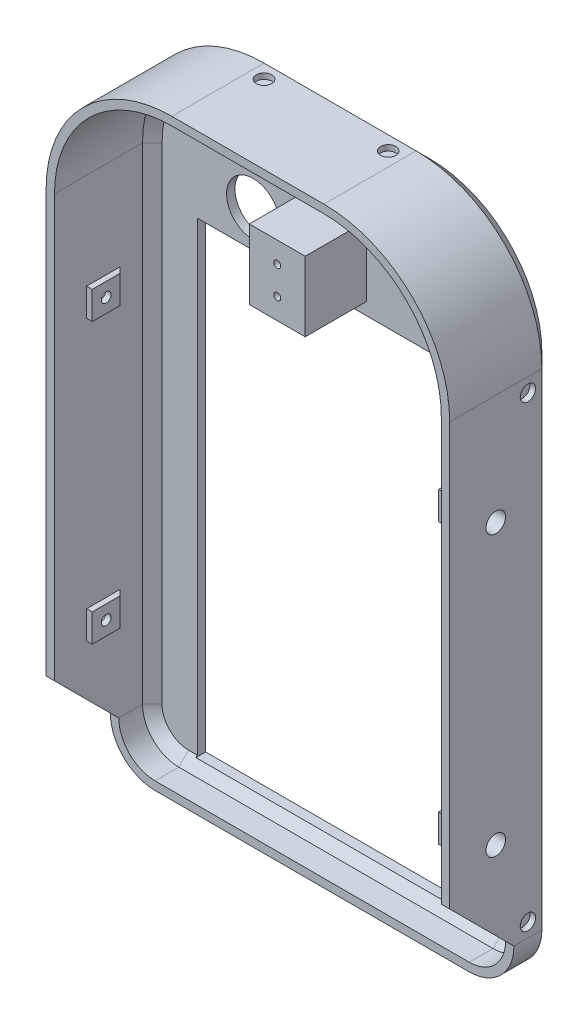
SolidWorks part; units mm, degrees
ref_plane "Plan de face" through (0, 0, 0) normal (0, 0, 1) x (1, 0, 0)
ref_plane "Plan de dessus" through (0, 0, 0) normal (0, 1, 0) x (1, 0, 0)
ref_plane "Plan de droite" through (0, 0, 0) normal (1, 0, 0) x (0, 0, -1)
sketch "Esquisse1" plane through (0, 0, 0) normal (0, 0, 1) x (1, 0, 0)
  line L1 (-12.2348, 13.2576) -> (7.7652, 13.2576)
  line L2 (-12.2348, 13.2576) -> (-12.2348, -11.7424)
  line L3 (-12.2348, -11.7424) -> (7.7652, -11.7424)
  line L4 (7.7652, 13.2576) -> (7.7652, -11.7424)
  dimension "D1" = 20
  dimension "D2" = 25
extrude "Boss.-Extru.1" add sketch "Esquisse1" along normal blind 22
sketch "Esquisse2" plane through (0, 0, 22) normal (0, 0, 1) x (1, 0, 0)
  line L0 (-12.2348, 0.7576) -> (7.7652, 0.7576) construction
  line L1 (-12.2348, 13.2576) -> (-12.2348, -11.7424) construction
  line L2 (7.7652, -11.7424) -> (7.7652, 13.2576) construction
  line L3 (-2.2348, 5.7576) -> (-2.2348, -4.2424) construction
  circle A0 centre (-2.2348, 5.7576) radius 1.25
  circle A1 centre (-2.2348, -4.2424) radius 1.25
  point P13 (-2.2348, 0.7576)
  point P14 (-2.2348, 0.7576)
  dimension "D2" = 2.5
  dimension "D1" = 10
extrude "Enlèv. mat.-Extru.1" cut sketch "Esquisse2" against normal blind 15
sketch "Esquisse3" plane through (0, 0, 0) normal (0, 0, -1) x (-1, 0, 0)
  line L1 (71.9648, -16.2424) -> (-72.4852, -16.2424)
  line L2 (71.9648, -16.2424) -> (71.9648, 45.7576)
  line L3 (71.9648, 45.7576) -> (-72.4852, 45.7576)
  line L4 (-72.4852, -16.2424) -> (-72.4852, 45.7576)
  line L5 (-7.7652, 13.2576) -> (12.2348, 13.2576) construction
  line L7 (12.2348, -11.7424) -> (-7.7652, -11.7424) construction
  line L8 (12.2348, 13.2576) -> (12.2348, -11.7424) construction
  line L9 (-7.7652, -11.7424) -> (-7.7652, 13.2576) construction
  dimension "D1" = 4.5
  dimension "D2" = 59.73
  dimension "D3" = 64.72
  dimension "D4" = 32.5
extrude "Wall" add sketch "Esquisse3" along normal blind 3
sketch "Esquisse4" plane through (0, 0, -3) normal (0, 0, -1) x (-1, 0, 0)
  line L1 (-72.4852, -16.2424) -> (71.9648, -16.2424) construction
  line L2 (12.2348, 13.2576) -> (12.2348, -11.7424) construction
  line L3 (-32.5352, 28.7576) -> (32.4648, 28.7576) construction
  line L4 (-32.5352, 39.2576) -> (32.4648, 39.2576)
  line L5 (-32.5352, 18.2576) -> (32.4648, 18.2576)
  line L7 (71.9648, -16.2424) -> (71.9648, 45.7576) construction
  circle A0 centre (32.8698, -3.4521) radius 9.5
  arc A1 (-32.5352, 39.2576) -> (-32.5352, 18.2576) centre (-32.5352, 28.7576) ccw
  arc A2 (32.4648, 18.2576) -> (32.4648, 39.2576) centre (32.4648, 28.7576) ccw
  point P8 (-0.0352, 28.7576)
  dimension "D1" = 19
  dimension "D7" = 10.5
  dimension "D2" = 20.635
  dimension "D3" = 12.7903
  dimension "D4" = 45
  dimension "D5" = 39.5
  dimension "D6" = 65
extrude "Cameras" cut sketch "Esquisse4" against normal up to next
sketch "Esquisse9" plane through (0, 0, -3) normal (0, 0, -1) x (-1, 0, 0)
  line L0 (-49.1352, -183.2424) -> (52.8648, -183.2424)
  line L1 (-72.4852, -16.2424) -> (-49.1352, -16.2424)
  line L2 (-72.4852, -16.2424) -> (-72.4852, -189.2424)
  line L4 (-49.1352, -16.2424) -> (-49.1352, -183.2424)
  line L5 (71.9648, -16.2424) -> (52.8648, -16.2424)
  line L6 (71.9648, -16.2424) -> (71.9648, -189.2424)
  line L8 (52.8648, -16.2424) -> (52.8648, -183.2424)
  line L9 (-72.4852, -189.2424) -> (71.9648, -189.2424)
  dimension "D1" = 23.35
  dimension "D2" = 19.1
  dimension "D3" = 167
  dimension "D4" = 6
extrude "Screen" add sketch "Esquisse9" against normal up to surface (3 mm away) up to face at (-42.3698, -3.4521, 0)
sketch "Esquisse5" plane through (0, 0, 0) normal (0, 0, 1) x (1, 0, 0)
  line L2 (-71.9648, -189.2424) -> (-71.9648, 45.7576)
  line L7 (72.4852, 45.7576) -> (72.4852, -189.2424)
  line L10 (-71.9648, 45.7576) -> (72.4852, 45.7576) construction
  line L11 (-71.9648, 45.7576) -> (72.4852, 45.7576)
  line L12 (-68.9648, -186.2424) -> (-68.9648, 42.7576)
  line L13 (-68.9648, 42.7576) -> (69.4852, 42.7576)
  line L14 (69.4852, 42.7576) -> (69.4852, -186.2424)
  line L15 (0.2602, 42.7576) -> (0.2602, 45.7576) construction
  line L18 (-71.9648, -189.2424) -> (72.4852, -189.2424) construction
  line L19 (-68.9648, -186.2424) -> (69.4852, -186.2424)
  line L20 (0.2602, -186.2424) -> (0.2602, -189.2424) construction
  line L21 (-68.9648, -186.2424) -> (-71.9648, -186.2424) construction
  line M11 (-71.9648, 45.7576) -> (-71.9648, -189.2424)
  line M13 (72.4852, -189.2424) -> (72.4852, 45.7576)
  line M14 (72.4852, 45.7576) -> (-71.9648, 45.7576)
  line M32 (-71.9648, -189.2424) -> (72.4852, -189.2424)
  dimension "D1" = 3
extrude "Boss.-Extru.3" add sketch "Esquisse5" along normal blind 35 contours L19 L12 L13 L14 M14 M11 M32 M13 region at (-69.2064, -71.7424, 0)
fillet "Congé1" radius 42 2 edges at (-68.9648, 42.7576, 17.5) (69.4852, 42.7576, 17.5)
fillet "Congé2" radius 45 2 edges at (-71.9648, 45.7576, 16) (72.4852, 45.7576, 16)
fillet "Congé3" radius 13 2 edges at (-68.9648, -186.2424, 17.5) (69.4852, -186.2424, 17.5)
fillet "Congé4" radius 16 2 edges at (-71.9648, -189.2424, 16) (72.4852, -189.2424, 16)
chamfer "Chanfrein1" distance 5 angle 45 8 edges at (-71.9648, -86.2424, -3) (-58.7847, 32.5774, -3) (0.2602, 45.7576, -3) (72.4852, -86.2424, -3) (59.305, 32.5774, -3) (-67.2786, -184.5561, -3) (0.2602, -189.2424, -3) (67.7989, -184.5561, -3)
chamfer "Chanfrein2" distance 3.5 angle 45 8 edges at (-68.9648, -86.2424, 0) (-56.6633, 30.4561, 0) (69.4852, -86.2424, 0) (0.2602, 42.7576, 0) (57.1836, 30.4561, 0) (-65.1572, -182.4348, 0) (0.2602, -186.2424, 0) (65.6775, -182.4348, 0)
sketch "Esquisse16" plane through (72.4852, 0, 0) normal (1, 0, 0) x (0, 0, -1)
  line L0 (-35, -150.2424) -> (-12, -173.2424)
  line L1 (-12, -173.2424) -> (-12, -189.2424)
  line L2 (-12, -189.2424) -> (-35, -189.2424)
  line L3 (-35, -189.2424) -> (-35, -150.2424)
  line L4 (-2, -189.2424) -> (-2, -173.2424) construction
  line L5 (-35, -189.2424) -> (-2, -189.2424) construction
  line L8 (-35, -173.2424) -> (-35, 0.7576) construction
  line L9 (-35, -173.2424) -> (-2, -173.2424) construction
  dimension "D1" = 10
  dimension "D2" = 45
extrude "Enlèv. mat.-Extru.9" cut sketch "Esquisse16" against normal through all
ref_plane "Plan1" through (0, 0, 13.5) normal (0, 0, 1) x (1, 0, 0)
sketch "Esquisse11" plane through (0, 0, 13.5) normal (0, 0, 1) x (1, 0, 0)
  line L1 (69.4852, -143.6314) -> (57.0352, -143.6314)
  line L3 (69.4852, -33.6314) -> (57.0352, -33.6314)
  line L5 (-66.9648, -143.6314) -> (-68.9648, -143.6314)
  line L7 (-66.9648, -33.6314) -> (-68.9648, -33.6314)
  line L9 (57.0352, -33.6314) -> (57.0352, -43.6314)
  line L10 (49.1352, -16.2424) -> (-52.8648, -16.2424) construction
  line L11 (57.0352, -43.6314) -> (69.4852, -43.6314)
  line L12 (69.4852, -43.6314) -> (69.4852, -33.6314)
  line L13 (69.4852, -173.2424) -> (69.4852, -150.2424) construction
  line L14 (57.0352, -143.6314) -> (57.0352, -133.6314)
  line L15 (57.0352, -133.6314) -> (69.4852, -133.6314)
  line L16 (69.4852, -133.6314) -> (69.4852, -143.6314)
  line L17 (-66.9648, -33.6314) -> (-66.9648, -43.6314)
  line L18 (-66.9648, -43.6314) -> (-68.9648, -43.6314)
  line L19 (-68.9648, -43.6314) -> (-68.9648, -33.6314)
  line L20 (-66.9648, -143.6314) -> (-66.9648, -133.6314)
  line L21 (-66.9648, -133.6314) -> (-68.9648, -133.6314)
  line L22 (-68.9648, -133.6314) -> (-68.9648, -143.6314)
  line L23 (-68.9648, -150.2424) -> (-68.9648, 0.7576) construction
  point P21 (57.0352, -138.6314)
  point P22 (57.0352, -38.6314)
  dimension "D1" = 12.45
  dimension "D2" = 2
  dimension "D3" = 10
  dimension "D4" = 100
  dimension "D5" = 22.3889
extrude "Boss.-Extru.5" add sketch "Esquisse11" along normal blind 10
chamfer "Chanfrein3" distance 2 angle 45 2 edges at (-68.9648, -38.6314, 13.5) (-68.9648, -138.6314, 13.5)
chamfer "Chanfrein4" distance 12.45 angle 45 2 edges at (69.4852, -38.6314, 13.5) (69.4852, -138.6314, 13.5)
sketch "Esquisse12" plane through (57.0352, 0, 0) normal (-1, 0, 0) x (0, 0, 1)
  line L1 (23.5, -33.6314) -> (23.5, -43.6314) construction
  line L3 (23.5, -33.6314) -> (13.5, -33.6314) construction
  circle A0 centre (18.5, -38.6314) radius 1.75
  circle A1 centre (18.5, -138.6314) radius 1.75
  point P10 (23.5, -38.6314)
  point P12 (18.5, -33.6314)
  dimension "D2" = 3.5
  dimension "D3" = 100
extrude "Enlèv. mat.-Extru.5" cut sketch "Esquisse12" against normal through all both and the other way through all
sketch "Esquisse13" plane through (-71.9648, 0, 0) normal (-1, 0, 0) x (0, 0, 1)
  circle A0 centre (18.5, -38.6314) radius 3.5
  circle A1 centre (18.5, -138.6314) radius 3.5
  dimension "D1" = 7
extrude "Enlèv. mat.-Extru.6" cut sketch "Esquisse13" against normal blind 3
sketch "Esquisse14" plane through (72.4852, 0, 0) normal (1, 0, 0) x (0, 0, -1)
  circle A2 centre (-18.5, -138.6314) radius 3.5 construction
  circle A3 centre (-18.5, -38.6314) radius 3.5 construction
  circle A4 centre (-18.5, -138.6314) radius 3.5
  circle A5 centre (-18.5, -38.6314) radius 3.5
extrude "Enlèv. mat.-Extru.7" cut sketch "Esquisse14" against normal offset from surface (13.45 mm away) 2 up to face at (57.0352, -38.6314, 16.75)
sketch "Esquisse6" plane through (0, 45.7576, 0) normal (0, 1, 0) x (1, 0, 0)
  line L1 (27.4852, -35) -> (27.4852, -2) construction
  line L2 (22.4852, -7) -> (27.4852, -7) construction
  line L4 (-21.9648, -7) -> (-26.9648, -7) construction
  line L5 (-26.9648, -2) -> (-26.9648, -35) construction
  line L7 (27.4852, -2) -> (-26.9648, -2) construction
  circle A0 centre (22.4852, -7) radius 2.75
  circle A1 centre (-21.9648, -7) radius 2.75
  dimension "D2" = 5.5
  dimension "D1" = 5
  dimension "D3" = 5
extrude "Enlèv. mat.-Extru.2" cut sketch "Esquisse6" against normal blind 2
sketch "Esquisse7" plane through (72.4852, 0, 0) normal (1, 0, 0) x (0, 0, -1)
  line L0 (-2, 0.7576) -> (-35, 0.7576) construction
  line L2 (-2, -173.2424) -> (-2, 0.7576) construction
  line L3 (-7, -168.2424) -> (-7, -173.2424) construction
  line L5 (-7, -4.2424) -> (-7, 0.7576) construction
  line L6 (-2, 0.7576) -> (-35, 0.7576) construction
  line L7 (-12, -173.2424) -> (-2, -173.2424) construction
  circle A0 centre (-7, -4.2424) radius 2.75
  circle A1 centre (-7, -168.2424) radius 2.75
  dimension "D1" = 5.5
  dimension "D2" = 5
  dimension "D3" = 5
extrude "Enlèv. mat.-Extru.3" cut sketch "Esquisse7" against normal blind 2
sketch "Esquisse8" plane through (-71.9648, 0, 0) normal (-1, 0, 0) x (0, 0, 1)
  circle A2 centre (7, -4.2424) radius 2.75 construction
  circle A3 centre (7, -168.2424) radius 2.75 construction
  circle A4 centre (7, -4.2424) radius 2.75
  circle A5 centre (7, -168.2424) radius 2.75
extrude "Enlèv. mat.-Extru.4" cut sketch "Esquisse8" against normal blind 2
sketch "Esquisse15" plane through (0, -189.2424, 0) normal (0, -1, 0) x (1, 0, 0)
  circle A0 centre (-21.9648, 7) radius 2.75 construction
  circle A1 centre (22.4852, 7) radius 2.75 construction
  circle A2 centre (-21.9648, 7) radius 2.75
  circle A3 centre (22.4852, 7) radius 2.75
extrude "Enlèv. mat.-Extru.8" cut sketch "Esquisse15" against normal blind 2
